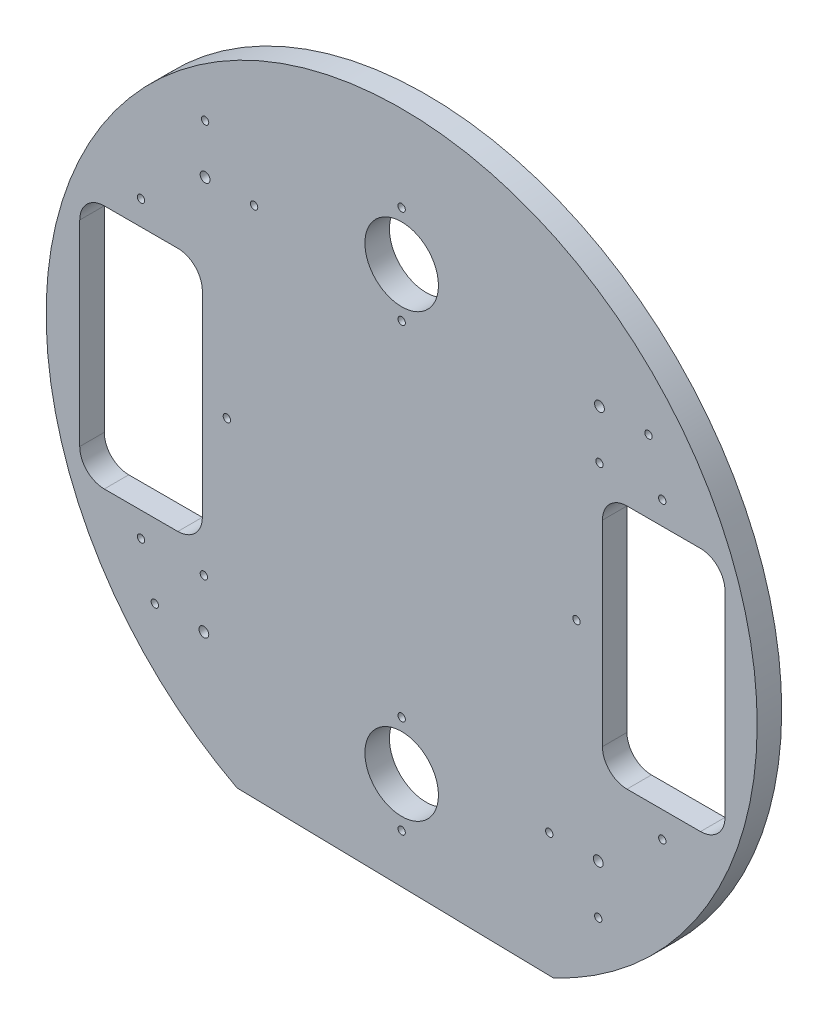
SolidWorks part; units mm, degrees
ref_plane "Front Plane" through (0, 0, 0) normal (0, 0, 1) x (1, 0, 0)
ref_plane "Top Plane" through (0, 0, 0) normal (0, 1, 0) x (1, 0, 0)
ref_plane "Right Plane" through (0, 0, 0) normal (1, 0, 0) x (0, 0, -1)
sketch "Sketch1" plane through (0, 0, 0) normal (0, 0, 1) x (1, 0, 0)
  line L0 (-90.1847, 90.6631) -> (-70.1847, 70.6631) construction
  line L1 (-91.2897, -50) -> (-121.2897, -50)
  line L2 (-81.2897, -40) -> (-81.2897, 40)
  line L3 (-91.2897, 50) -> (-121.2897, 50)
  line L4 (-131.2897, -40) -> (-131.2897, 40)
  line L5 (-90.1847, 70.6631) -> (-70.1847, 90.6631) construction
  line L32 (91.8758, 50.5861) -> (121.8758, 50.5861)
  line L33 (131.8758, -39.4139) -> (131.8758, 40.5861)
  line L34 (91.8758, -49.4139) -> (121.8758, -49.4139)
  line L35 (81.8758, -39.4139) -> (81.8758, 40.5861)
  line L36 (-67.1096, -128.5352) -> (61.8877, -131.1294)
  line L38 (-182.6953, 0) -> (151.1139, 0) construction
  line L43 (-80.1699, 148.2905) -> (-80.1699, 80.6692) construction
  line L44 (-80.1699, 80.6692) -> (-60.1847, 80.6692) construction
  arc A0 (61.8877, -131.1294) -> (-67.1096, -128.5352) centre (0, 0) ccw
  circle A1 centre (-80.1699, 80.6692) radius 2
  circle A2 centre (-80.1699, 100.6631) radius 1.5
  circle A3 centre (-60.1847, 80.6692) radius 1.5
  circle A4 centre (-106.2897, 60) radius 1.5
  circle A5 centre (-71.2897, 0) radius 1.5
  circle A6 centre (-106.2897, -60) radius 1.5
  circle A13 centre (80.6692, 80.1699) radius 2
  circle A14 centre (80.6692, 60.1847) radius 1.5
  circle A15 centre (100.6631, 80.1699) radius 1.5
  circle A16 centre (80.1699, -80.6692) radius 2
  circle A17 centre (60.1847, -80.6692) radius 1.5
  circle A18 centre (80.1699, -100.6631) radius 1.5
  circle A19 centre (-80.6692, -80.1699) radius 2
  circle A20 centre (-80.6692, -60.1847) radius 1.5
  circle A21 centre (-100.6631, -80.1699) radius 1.5
  circle A22 centre (106.2897, 60) radius 1.5
  circle A23 centre (106.2897, -60) radius 1.5
  circle A24 centre (71.2897, 0) radius 1.5
  circle A53 centre (0, 90) radius 15
  circle A54 centre (0, 70) radius 1.5
  circle A55 centre (0, 110) radius 1.5
  arc A59 (-131.2897, -40) -> (-121.2897, -50) centre (-121.2897, -40) ccw
  arc A60 (-91.2897, -50) -> (-81.2897, -40) centre (-91.2897, -40) ccw
  arc A61 (-81.2897, 40) -> (-91.2897, 50) centre (-91.2897, 40) ccw
  arc A62 (-131.2897, 40) -> (-121.2897, 50) centre (-121.2897, 40) cw
  arc A63 (81.8758, -39.4139) -> (91.8758, -49.4139) centre (91.8758, -39.4139) ccw
  arc A64 (121.8758, -49.4139) -> (131.8758, -39.4139) centre (121.8758, -39.4139) ccw
  arc A65 (131.8758, 40.5861) -> (121.8758, 50.5861) centre (121.8758, 40.5861) ccw
  arc A66 (81.8758, 40.5861) -> (91.8758, 50.5861) centre (91.8758, 40.5861) cw
  circle A70 centre (0, -70) radius 1.5
  circle A71 centre (0, -110) radius 1.5
  circle A72 centre (0, -90) radius 15
  point P3 (-15.7907, 0)
  point P4 (0, 0)
  point P5 (0, 0)
  point P6 (0, 0)
  point P12 (0, 0)
  point P13 (0, 0)
  point P38 (0, 0)
  point P39 (0, 0)
  point P41 (0, 0)
  point P42 (0, 0)
  point P140 (81.8758, -49.4139)
  point P143 (131.8758, -49.4139)
  point P146 (131.8758, 50.5861)
  point P149 (81.8758, 50.5861)
  point P154 (-15.7907, 0)
  dimension "D1" = 50
  dimension "D4" = 90
  dimension "D6" = 10
  dimension "D9" = 10
  dimension "D10" = 20
  dimension "D22" = 10
  dimension "D23" = 10
  dimension "D5" = 20
  dimension "D2" = 20
  dimension "D3" = 20
  dimension "D7" = 100
  dimension "D8" = 10
  dimension "D13" = 4
extrude "Boss-Extrude1" add sketch "Sketch1" along normal blind 10 contours L36 A0 A23 A2 A3 A4 A5 A6 A70 region at (0.0135, 3.3024, 0)
